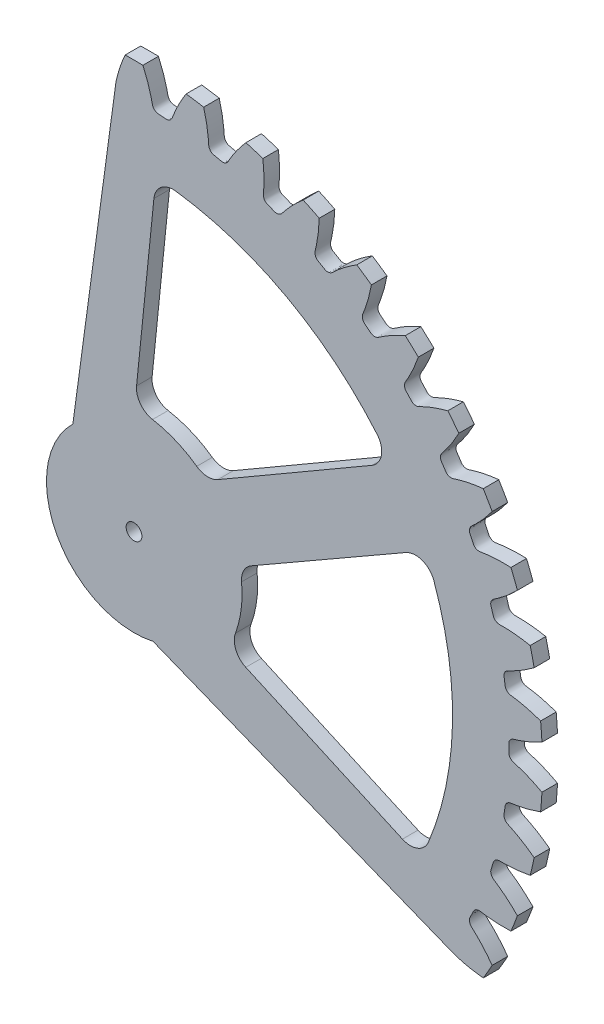
SolidWorks part; units mm, degrees
ref_plane "Front Plane" through (0, 0, 0) normal (0, 0, 1) x (1, 0, 0)
ref_plane "Top Plane" through (0, 0, 0) normal (0, 1, 0) x (1, 0, 0)
ref_plane "Right Plane" through (0, 0, 0) normal (1, 0, 0) x (0, 0, -1)
ref_axis "Axis1" through (0, 0, 4.4) along (0, 0, -1)
sketch "SketchRevolveGeartrax1Pinion" plane through (0, 0, 0) normal (1, 0, 0) x (0, 0, -1)
  line L0 (0, 0) -> (1, 0) construction
  line L1 (-4, 0) -> (-4, 209.9802)
  line L2 (-4, 209.9802) -> (4, 209.9802)
  line L3 (4, 209.9802) -> (4, 0)
  line L4 (4, 0) -> (-4, 0)
  dimension "Side1" = 4
  dimension "OutsideRadius" = 209.9802
  dimension "Side2" = 4
revolve "Geartrax1Pinion" add sketch "SketchRevolveGeartrax1Pinion" angle 360 about L0
sketch "SketchToothGeartrax1Pinion" plane through (0, 0, 0) normal (0, 0, 1) x (1, 0, 0)
  arc A0 (210.0599, 11.334) -> (210.0599, -11.334) centre (0, 0) cw
  spline S0 degree 3 poles (210.0599, -11.334) (209.4217, -10.9881) (208.4711, -10.4875) (207.2086, -9.8529) (206.2955, -9.408) (205.4033, -8.9869) (204.5325, -8.589) (203.6837, -8.2138) (202.8572, -7.8607) (202.0533, -7.529) (201.2727, -7.2181) (200.5155, -6.9274) (199.7822, -6.6563) (199.0732, -6.404) (198.3887, -6.1702) (197.7293, -5.9536) (197.0948, -5.7551) (196.207, -5.483) (195.4417, -5.3001) (194.8373, -5.0557) (194.6186, -4.9551) (194.3918, -4.8357) (194.154, -4.6908) (193.9022, -4.5108) (193.6355, -4.2818) (193.3577, -3.9861) (193.0818, -3.6032) (192.8378, -3.1183) (192.6687, -2.5501) (192.5961, -1.4951) (192.6776, 0) (192.5961, 1.4951) (192.6687, 2.5501) (192.8378, 3.1183) (193.0818, 3.6032) (193.3577, 3.9861) (193.6355, 4.2818) (193.9022, 4.5108) (194.154, 4.6908) (194.3918, 4.8357) (194.6186, 4.9551) (194.8373, 5.0557) (195.4417, 5.3001) (196.207, 5.483) (197.0948, 5.7551) (197.7293, 5.9536) (198.3887, 6.1702) (199.0732, 6.404) (199.7822, 6.6563) (200.5155, 6.9274) (201.2727, 7.2181) (202.0533, 7.529) (202.8572, 7.8607) (203.6837, 8.2138) (204.5325, 8.589) (205.4033, 8.9869) (206.2955, 9.408) (207.2086, 9.8529) (208.4711, 10.4875) (209.4217, 10.9881) (210.0599, 11.334) knots 0 0 0 0 0.04842 0.071654 0.094238 0.116172 0.137455 0.158088 0.178071 0.197403 0.216085 0.234117 0.251499 0.26823 0.284311 0.299741 0.314521 0.328651 0.361696 0.366792 0.372106 0.377751 0.383874 0.390667 0.398374 0.40728 0.417674 0.429733 0.443337 0.456892 0.5 0.543108 0.556663 0.570267 0.582326 0.59272 0.601626 0.609333 0.616126 0.622249 0.627894 0.633208 0.638304 0.671349 0.685479 0.700259 0.715689 0.73177 0.748501 0.765883 0.783915 0.802597 0.821929 0.841912 0.862545 0.883828 0.905762 0.928346 0.95158 1 1 1 1
extrude "ToothExtrudeCutGeartrax1Pinion" cut sketch "SketchToothGeartrax1Pinion" against normal blind 4 and the other way blind 4
pattern_circular "PatternGeartrax1Pinion" count 42 every 8.571 about axis through (0, 0, 4.4) along (0, 0, -1) of "ToothExtrudeCutGeartrax1Pinion"
sketch "BoreRevolveSketch" plane through (0, 0, 0) normal (1, 0, 0) x (0, 0, -1)
  line L0 (0, 0) -> (1, 0) construction
  line L1 (-4, 0) -> (4, 0)
  line L2 (4, 0) -> (4, 4.05)
  line L3 (4, 4.05) -> (-4, 4.05)
  line L4 (-4, 4.05) -> (-4, 0)
  dimension "BoreSide1" = 4
  dimension "TaperSide1" = 4.05
  dimension "BoreSide2" = 4
  dimension "TaperSide2" = 4.05
revolve "BoreRevolveCut" cut sketch "BoreRevolveSketch" angle 360 about L0
sketch "AuxiliarySketchGeartrax1Pinion" plane through (0, 0, 0) normal (0, 0, 1) x (1, 0, 0)
  circle A0 centre (0, 0) radius 202.2745 construction
  circle A1 centre (0, 0) radius 190.0759 construction
  circle A2 centre (0, 0) radius 195.6998 construction
  circle A3 centre (0, 0) radius 209.9802 construction
  circle A4 centre (0, 0) radius 192.6424 construction
  dimension "PitchDiameter" = 404.549
  dimension "BaseDiameter" = 380.1517
  dimension "FormDiameter" = 391.3995
  dimension "MajorDiameter" = 419.9604
  dimension "MinorDiameter" = 385.2848
sketch "Sketch1" plane through (0, 0, 4) normal (0, 0, 1) x (1, 0, 0)
  line L0 (0, 0) -> (-9.9808, 209.7429)
  line L1 (0, 0) -> (176.6523, -113.515)
  arc A1 (176.6523, -113.515) -> (-9.9808, 209.7429) centre (0, 0) ccw
  circle A4 centre (0, 0) radius 209.9802 construction
  dimension "D2" = 9.9808
  dimension "D1" = 125.449
extrude "Cut-Extrude1" cut sketch "Sketch1" against normal through all flip side to cut
sketch "Sketch2" plane through (0, 0, 4) normal (0, 0, 1) x (1, 0, 0)
  line L0 (-9.302, 195.4786) -> (-31.4327, 32.2022)
  line L1 (164.6384, -105.795) -> (9.7693, -43.9268)
  line L2 (-9.302, 195.4786) -> (0, 45)
  line L3 (164.6384, -105.795) -> (45, 0)
  arc A0 (-31.4327, 32.2022) -> (9.7693, -43.9268) centre (0, 0) ccw
  circle A1 centre (0, 0) radius 4.05
  arc A2 (45, 0) -> (0, 45) centre (0, 0) ccw
  arc A4 (3.4072, -2.1894) -> (-0.1925, 4.0454) centre (0, 0) ccw construction
  dimension "D1" = 90
extrude "Boss-Extrude1" add sketch "Sketch2" against normal blind 8
sketch "Sketch3" plane through (0, 0, 4) normal (0, 0, 1) x (1, 0, 0)
  line L0 (0, 0) -> (181.8482, 104.9901) construction
  line L1 (147.0921, -71.9568) -> (48.2477, -27.5191)
  line L3 (11.2296, 163.3639) -> (0.2916, 55.5433)
  line L4 (37.1547, 41.2877) -> (132.2984, 96.4935)
  line L5 (54.3335, 11.5331) -> (149.715, 66.327)
  arc A0 (184.0896, 101.0083) -> (179.5206, 108.9221) centre (0, 0) ccw construction
  arc A1 (147.0921, -71.9568) -> (149.715, 66.327) centre (0, 0) ccw
  arc A2 (48.2477, -27.5191) -> (54.3335, 11.5331) centre (0, 0) ccw
  arc A3 (37.1547, 41.2877) -> (0.2916, 55.5433) centre (0, 0) ccw
  arc A4 (132.2984, 96.4935) -> (11.2296, 163.3639) centre (0, 0) ccw
  dimension "D1" = 110
extrude "Cut-Extrude2" cut sketch "Sketch3" against normal through all
fillet "Fillet1" radius 10 8 edges at (147.0921, -71.9568, 0) (48.2477, -27.5191, 0) (54.3335, 11.5331, 0) (149.715, 66.327, 0) (11.2296, 163.3639, 0) (132.2984, 96.4935, 0) (37.1547, 41.2877, 0) (0.2916, 55.5433, 0)
